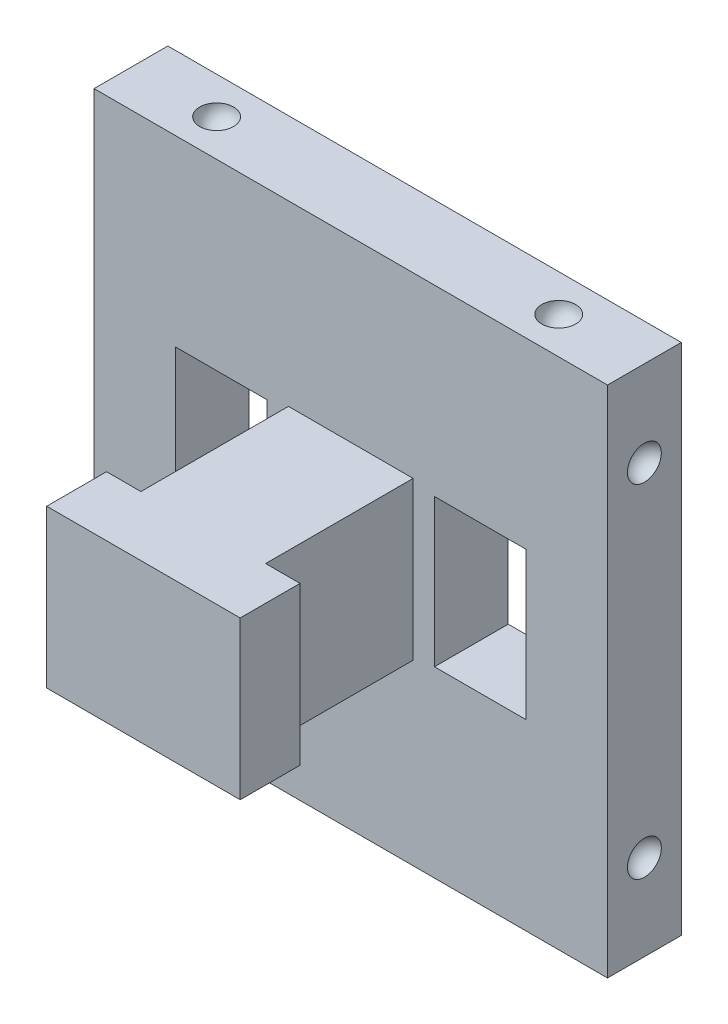
SolidWorks part; units mm, degrees
ref_plane "正面" through (0, 0, 0) normal (0, 0, 1) x (1, 0, 0)
ref_plane "平面" through (0, 0, 0) normal (0, 1, 0) x (1, 0, 0)
ref_plane "右側面" through (0, 0, 0) normal (1, 0, 0) x (0, 0, -1)
sketch "ｽｹｯﾁ1" plane through (0, 0, 0) normal (0, 0, 1) x (1, 0, 0)
  line L0 (6.375, 23.65) -> (6.375, 0) construction
  line L1 (0, 0) -> (12.75, 0)
  line L2 (0, 0) -> (0, 23.65)
  line L3 (0, 23.65) -> (12.75, 23.65)
  line L4 (12.75, 0) -> (12.75, 23.65) construction
  line L5 (19.375, 23.65) -> (19.375, 0) construction
  line L6 (12.75, 23.65) -> (25.755, 23.65)
  line L7 (12.75, 0) -> (25.755, 0)
  line L8 (25.755, 0) -> (25.755, 23.65)
  line L9 (12.75, 11.825) -> (0, 11.825) construction
  dimension "D2" = 12.75
  dimension "D3" = 13
  dimension "D4" = 6.38
extrude "ﾎﾞｽ - 押し出し1" add sketch "ｽｹｯﾁ1" along normal blind 3.7
sketch "ｽｹｯﾁ2" plane through (0, 0, 3.7) normal (0, 0, 1) x (1, 0, 0)
  line L0 (12.8775, 23.65) -> (12.8775, 0) construction
  line L1 (19.375, 15.525) -> (19.375, 23.65) construction
  line L2 (8.68, 15.525) -> (8.68, 8.125)
  line L3 (17.075, 15.525) -> (17.075, 8.125)
  line L4 (4.08, 15.525) -> (8.68, 15.525)
  line L5 (4.08, 15.525) -> (4.08, 8.125)
  line L6 (4.08, 8.125) -> (8.68, 8.125)
  line L9 (6.38, 23.65) -> (6.38, 0) construction
  line L10 (25.755, 23.65) -> (0, 23.65) construction
  line L11 (0, 0) -> (25.755, 0) construction
  line L12 (0, 23.65) -> (0, 0) construction
  line L13 (21.675, 8.125) -> (17.075, 8.125)
  line L14 (21.675, 15.525) -> (21.675, 8.125)
  line L15 (21.675, 15.525) -> (17.075, 15.525)
  dimension "D5" = 6.38
extrude "ｶｯﾄ - 押し出し1" cut sketch "ｽｹｯﾁ2" against normal up to next
sketch "ｽｹｯﾁ3" plane through (0, 0, 3.7) normal (0, 0, 1) x (1, 0, 0)
  line L1 (25.755, 0) -> (25.755, 23.65) construction
  line L2 (0, 23.65) -> (25.755, 23.65)
  line L3 (0, 23.65) -> (0, 21.65)
  line L4 (0, 21.65) -> (25.755, 21.65)
  line L5 (25.755, 23.65) -> (25.755, 21.65)
  line L7 (0, 0) -> (25.755, 0)
  line L8 (0, 0) -> (0, 2)
  line L9 (0, 2) -> (25.755, 2)
  line L10 (25.755, 0) -> (25.755, 2)
  dimension "D1" = 2
  dimension "D2" = 2
extrude "ﾎﾞｽ - 押し出し2" add sketch "ｽｹｯﾁ3" along normal blind 1
sketch "ｽｹｯﾁ4" plane through (0, 0, 3.7) normal (0, 0, 1) x (1, 0, 0)
  line L0 (8.68, 8.125) -> (8.68, 15.525) construction
  line L1 (0, 21.65) -> (0, 2) construction
  line L2 (9.75, 7.875) -> (16.005, 7.875)
  line L3 (12.8775, 15.525) -> (12.8775, 21.65) construction
  line L4 (0, 15.775) -> (2.95, 15.775)
  line L5 (0, 15.775) -> (0, 7.875)
  line L6 (0, 7.875) -> (2.95, 7.875)
  line L7 (2.95, 15.775) -> (2.95, 7.875)
  line L8 (9.75, 15.775) -> (9.75, 7.875)
  line L9 (0, 21.65) -> (25.755, 21.65) construction
  line L10 (16.005, 15.775) -> (16.005, 7.875)
  line L11 (9.75, 15.775) -> (16.005, 15.775)
  line L12 (17.075, 15.525) -> (17.075, 8.125) construction
  line L13 (0, 5.152) -> (25.755, 5.152) construction
  line L14 (25.755, 2) -> (25.755, 21.65) construction
  line L15 (12.8775, 5.152) -> (12.8775, 25.6744) construction
  line L16 (22.805, 15.775) -> (22.805, 7.875)
  line L17 (25.755, 7.875) -> (22.805, 7.875)
  line L18 (25.755, 15.775) -> (25.755, 7.875)
  line L19 (25.755, 15.775) -> (22.805, 15.775)
  dimension "D1" = 1.07
  dimension "D2" = 1.07
  dimension "D3" = 2.95
extrude "ﾎﾞｽ - 押し出し3" add sketch "ｽｹｯﾁ4" along normal blind 10.4
sketch "ｽｹｯﾁ5" plane through (0, 0, 14.1) normal (0, 0, 1) x (1, 0, 0)
  line L0 (12.8775, 21.65) -> (12.8775, 26.6538) construction
  line L6 (3, 11.825) -> (9.75, 11.825) construction
  line L7 (9.75, 15.775) -> (9.75, 7.875) construction
  line L8 (6.375, 11.825) -> (6.375, 21.65) construction
  line L9 (16.005, 15.775) -> (17.73, 15.775)
  line L10 (0, 21.65) -> (25.755, 21.65) construction
  line L11 (8.025, 15.775) -> (8.025, 7.875)
  line L12 (9.75, 7.875) -> (8.025, 7.875)
  line L13 (9.75, 15.775) -> (9.75, 7.875)
  line L14 (9.75, 15.775) -> (8.025, 15.775)
  line L15 (16.005, 15.775) -> (16.005, 7.875)
  line L16 (16.005, 7.875) -> (17.73, 7.875)
  line L17 (17.73, 15.775) -> (17.73, 7.875)
extrude "ﾎﾞｽ - 押し出し4" add sketch "ｽｹｯﾁ5" against normal blind 3
sketch "ｽｹｯﾁ9" plane through (0, 7.875, 0) normal (0, -1, 0) x (1, 0, 0)
  line L0 (0, 4.7) -> (2.95, 4.7)
  line L1 (0, 4.7) -> (25.755, 4.7) construction
  line L2 (22.805, 4.7) -> (25.755, 4.7)
  line L4 (0, 3.7) -> (2.95, 3.7)
  line L5 (2.95, 3.7) -> (2.95, 14.1)
  line L6 (2.95, 14.1) -> (0, 14.1)
  line L7 (0, 14.1) -> (0, 3.7)
  line L9 (2.95, 4.7) -> (2.95, 14.1)
  line L10 (2.95, 14.1) -> (0, 14.1)
  line L11 (0, 14.1) -> (0, 4.7)
  line L12 (22.805, 3.7) -> (25.755, 3.7)
  line L13 (25.755, 3.7) -> (25.755, 14.1)
  line L14 (25.755, 14.1) -> (22.805, 14.1)
  line L15 (22.805, 14.1) -> (22.805, 3.7)
  line L17 (25.755, 4.7) -> (25.755, 14.1)
  line L18 (25.755, 14.1) -> (22.805, 14.1)
  line L19 (22.805, 14.1) -> (22.805, 4.7)
  dimension "D1" = 0
  dimension "D2" = 0
extrude "ｶｯﾄ - 押し出し4" cut sketch "ｽｹｯﾁ9" against normal up to vertex (7.9 mm away) up to point (0, 15.775, 14.1)
fillet "ﾌｨﾚｯﾄ2" radius 0.4 2 edges at (22.805, 11.825, 4.7) (2.95, 11.825, 4.7)
sketch "ｽｹｯﾁ10" plane through (0, 0, 0) normal (-1, 0, 0) x (0, 0, 1)
  line L0 (4.7, 23.65) -> (0, 23.65) construction
  line L1 (4.7, 23.65) -> (2.079, 23.65)
  line L2 (4.7, 23.65) -> (4.7, 25.15)
  line L3 (4.7, 25.15) -> (2.079, 25.15)
  line L4 (2.079, 23.65) -> (2.079, 25.15)
  line L5 (4.7, 23.65) -> (4.7, 21.65) construction
  line L6 (0, 11.825) -> (-6.9736, 11.825) construction
  line L7 (4.7, -1.5) -> (2.079, -1.5)
  line L8 (4.7, 0) -> (4.7, -1.5)
  line L9 (4.7, 0) -> (2.079, 0)
  line L10 (2.079, 0) -> (2.079, -1.5)
  dimension "D1" = 1.5
extrude "ﾎﾞｽ - 押し出し5" [suppressed] add sketch "ｽｹｯﾁ10" against normal up to vertex up to point (25.755, 23.65, 4.7)
sketch "ｽｹｯﾁ11" plane through (0, 7.875, 0) normal (0, -1, 0) x (1, 0, 0)
  line L0 (2.95, 3.7) -> (2.95, 4.3) construction
  line L1 (2.55, 4.7) -> (0, 4.7) construction
  line L2 (0, 4.7) -> (0, 3.7) construction
  line L3 (0, 3.7) -> (2.95, 3.7) construction
  line L4 (25.755, 4.7) -> (23.205, 4.7) construction
  line L5 (22.805, 4.3) -> (22.805, 3.7) construction
  line L6 (22.805, 3.7) -> (25.755, 3.7) construction
  line L7 (25.755, 3.7) -> (25.755, 4.7) construction
  line L8 (2.95, 3.7) -> (2.95, 4.3)
  line L9 (2.55, 4.7) -> (0, 4.7)
  line L10 (0, 4.7) -> (0, 3.7)
  line L11 (0, 3.7) -> (2.95, 3.7)
  line L12 (25.755, 4.7) -> (23.205, 4.7)
  line L13 (22.805, 4.3) -> (22.805, 3.7)
  line L14 (22.805, 3.7) -> (25.755, 3.7)
  line L15 (25.755, 3.7) -> (25.755, 4.7)
  arc A0 (2.95, 4.3) -> (2.55, 4.7) centre (2.55, 4.3) ccw construction
  arc A1 (23.205, 4.7) -> (22.805, 4.3) centre (23.205, 4.3) ccw construction
  arc A2 (2.95, 4.3) -> (2.55, 4.7) centre (2.55, 4.3) ccw
  arc A3 (23.205, 4.7) -> (22.805, 4.3) centre (23.205, 4.3) ccw
extrude "ｶｯﾄ - 押し出し5" cut sketch "ｽｹｯﾁ11" against normal up to vertex (7.9 mm away) up to point (0, 15.775, 4.7)
sketch "ｽｹｯﾁ12" plane through (0, 0, 0) normal (-1, 0, 0) x (0, 0, 1)
  line L0 (3.7, 21.65) -> (3.7, 23.65)
  line L1 (3.7, 2) -> (3.7, 0)
  line L8 (4.7, 2) -> (3.7, 2)
  line L9 (3.7, 2) -> (3.7, 21.65)
  line L10 (3.7, 21.65) -> (4.7, 21.65)
  line L11 (4.7, 21.65) -> (4.7, 23.65)
  line L12 (4.7, 23.65) -> (0, 23.65)
  line L13 (0, 23.65) -> (0, 0)
  line L14 (0, 0) -> (4.7, 0)
  line L15 (4.7, 0) -> (4.7, 2)
  line L16 (4.7, 2) -> (3.7, 2)
  line L18 (3.7, 21.65) -> (4.7, 21.65)
  line L19 (4.7, 21.65) -> (4.7, 23.65)
  line L20 (4.7, 23.65) -> (3.7, 23.65)
  line L22 (3.7, 0) -> (4.7, 0)
  line L23 (4.7, 0) -> (4.7, 2)
  dimension "D1" = 0
extrude "ｶｯﾄ - 押し出し6" cut sketch "ｽｹｯﾁ12" against normal up to vertex (25.755 mm away) up to point (25.755, 21.65, 4.7)
sketch "ｽｹｯﾁ13" plane through (0, 0, 0) normal (0, 0, -1) x (-1, 0, 0)
  line L0 (0, 24.705) -> (-25.755, 24.705)
  line L2 (-25.755, -1.055) -> (0, -1.055)
  line L4 (0, 0) -> (0, 23.65)
  line L5 (0, 23.65) -> (-25.755, 23.65)
  line L6 (-25.755, 23.65) -> (-25.755, 0)
  line L7 (-25.755, 0) -> (0, 0)
  line L9 (0, 23.65) -> (-25.755, 23.65)
  line L10 (-26.81, -1.055) -> (1.055, -1.055) construction
  line L11 (-25.755, 0) -> (0, 0)
  line L12 (-25.755, 23.65) -> (-25.755, 24.705)
  line L13 (0, 23.65) -> (0, 24.705)
  line L14 (0, 0) -> (0, -1.055)
  line L15 (-25.755, 0) -> (-25.755, -1.055)
  line L16 (-26.81, 24.705) -> (-26.81, -1.055) construction
  line L17 (1.055, 24.705) -> (-26.81, 24.705) construction
  line L18 (-25.755, 23.65) -> (-25.755, 0) construction
  line L19 (1.055, -1.055) -> (1.055, 24.705) construction
  line L20 (0, 0) -> (0, 23.65) construction
  dimension "D2" = 23.65
  dimension "D3" = 1.055
  dimension "D1" = 0
extrude "ﾎﾞｽ - 押し出し6" add sketch "ｽｹｯﾁ13" against normal up to vertex (3.7 mm away) up to point (0, 23.65, 3.7)
sketch "ｽｹｯﾁ14" plane through (25.755, 0, 0) normal (1, 0, 0) x (0, 0, -1)
  line L0 (-1.85, 21.255) -> (-1.85, 19.555)
  line L1 (-3.7, 24.705) -> (0, 24.705) construction
  line L3 (-8.6565, 20.405) -> (-1.85, 20.405) construction
  line L4 (0, 11.825) -> (8.6335, 11.825) construction
  line L5 (0, -1.055) -> (0, 24.705) construction
  line L6 (-1.85, 2.395) -> (-1.85, 4.095)
  arc A0 (-1.85, 21.255) -> (-1.85, 19.555) centre (-1.85, 20.405) ccw
  arc A1 (-1.85, 2.395) -> (-1.85, 4.095) centre (-1.85, 3.245) cw
  dimension "D2" = 1.7
  dimension "D1" = 4.3
revolve "ｶｯﾄ - 回転1" cut sketch "ｽｹｯﾁ14" angle 180 about L0
ref_plane "平面1" through (12.8775, 0, 0) normal (1, 0, 0) x (0, 0, -1)
mirror "ﾐﾗｰ1" about plane through (12.8775, 0, 0) normal (1, 0, 0) of "ｶｯﾄ - 回転1"
sketch "ｽｹｯﾁ15" plane through (0, 24.705, 0) normal (0, 1, 0) x (1, 0, 0)
  line L0 (3.4475, -1.85) -> (5.1475, -1.85)
  line L1 (4.2975, -8.6565) -> (4.2975, -1.85) construction
  line L2 (12.8775, 0) -> (12.8775, 8.6335) construction
  line L3 (22.3075, -1.85) -> (20.6075, -1.85)
  arc A0 (3.4475, -1.85) -> (5.1475, -1.85) centre (4.2975, -1.85) ccw
  arc A1 (22.3075, -1.85) -> (20.6075, -1.85) centre (21.4575, -1.85) cw
revolve "ｶｯﾄ - 回転2" cut sketch "ｽｹｯﾁ15" angle 360 mid plane about L0
ref_plane "平面2" through (0, 11.825, 0) normal (0, -1, 0) x (-1, 0, 0)
mirror "ﾐﾗｰ2" about plane through (0, 11.825, 0) normal (0, -1, 0) of "ｶｯﾄ - 回転2"
